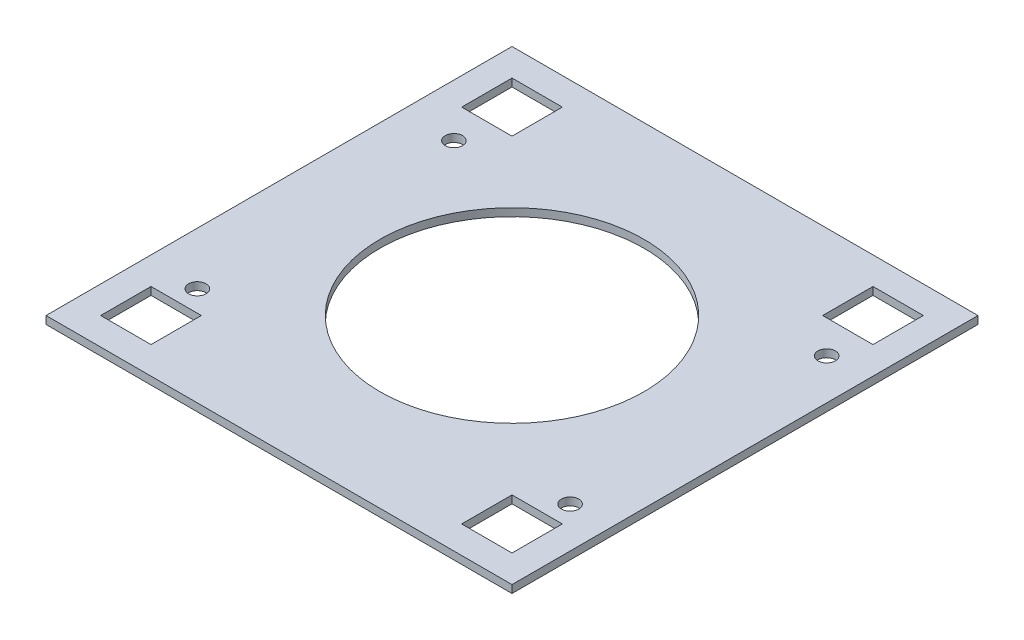
SolidWorks part; units mm, degrees
ref_plane "Front Plane" through (0, 0, 0) normal (0, 0, 1) x (1, 0, 0)
ref_plane "Top Plane" through (0, 0, 0) normal (0, 1, 0) x (1, 0, 0)
ref_plane "Right Plane" through (0, 0, 0) normal (1, 0, 0) x (0, 0, -1)
sketch "Sketch1" plane through (0, 0, 0) normal (0, 1, 0) x (1, 0, 0)
  line L1 (-190.5, 190.5) -> (190.5, 190.5)
  line L2 (-190.5, 190.5) -> (-190.5, -190.5)
  line L3 (-190.5, -190.5) -> (190.5, -190.5)
  line L4 (190.5, 190.5) -> (190.5, -190.5)
  line L5 (-190.5, 190.5) -> (190.5, -190.5) construction
  line L6 (-190.5, -190.5) -> (190.5, 190.5) construction
  point P0 (0, 0)
  dimension "D1" = 381
extrude "Boss-Extrude1" add sketch "Sketch1" along normal blind 6.35
sketch "Sketch2" plane through (0, 6.35, 0) normal (0, 1, 0) x (1, 0, 0)
  circle A0 centre (0, 0) radius 107.95
  dimension "D1" = 215.9
extrude "Cut-Extrude1" cut sketch "Sketch2" against normal blind 6.35
sketch "Sketch3" plane through (0, 6.35, 0) normal (0, 1, 0) x (1, 0, 0)
  line L0 (-190.5, 190.5) -> (190.5, -190.5) construction
  line L1 (127, 127) -> (168.148, 127)
  line L2 (-127, 127) -> (-168.148, 127)
  line L3 (0, 0) -> (0, 50000) construction
  line L4 (0, 0) -> (50000, 0) construction
  line L5 (-190.5, -190.5) -> (190.5, 190.5) construction
  line L6 (147.574, -147.574) -> (-147.574, -147.574) construction
  line L7 (147.574, -147.574) -> (147.574, 147.574) construction
  line L8 (147.574, 147.574) -> (-147.574, 147.574) construction
  line L9 (-147.574, -147.574) -> (-147.574, 147.574) construction
  line L10 (147.574, -147.574) -> (-147.574, 147.574) construction
  line L11 (147.574, 147.574) -> (-147.574, -147.574) construction
  line L12 (-127, 127) -> (-127, 168.148)
  line L13 (-127, 168.148) -> (-168.148, 168.148)
  line L14 (-168.148, 127) -> (-168.148, 168.148)
  line L15 (-127, 127) -> (-168.148, 168.148) construction
  line L16 (-127, 168.148) -> (-168.148, 127) construction
  line L17 (127, 127) -> (127, 168.148)
  line L18 (127, 168.148) -> (168.148, 168.148)
  line L19 (168.148, 127) -> (168.148, 168.148)
  line L20 (127, -127) -> (127, -168.148)
  line L21 (127, -127) -> (168.148, -127)
  line L22 (168.148, -127) -> (168.148, -168.148)
  line L23 (127, -168.148) -> (168.148, -168.148)
  line L24 (-127, -127) -> (-168.148, -127)
  line L25 (-127, -127) -> (-127, -168.148)
  line L26 (-127, -168.148) -> (-168.148, -168.148)
  line L27 (-168.148, -127) -> (-168.148, -168.148)
  line L28 (-147.574, 100.076) -> (157.226, 100.076) construction
  line L29 (-147.574, 100.076) -> (-147.574, -109.728) construction
  circle A4 centre (-147.574, 100.076) radius 7.112
  circle A5 centre (157.226, 100.076) radius 7.112
  circle A6 centre (157.226, -109.728) radius 7.112
  circle A7 centre (-147.574, -109.728) radius 7.112
  point P0 (0, 0)
  point P10 (0, 0)
  point P34 (0, 0)
  dimension "D2" = 41.148
  dimension "D5" = 14.224
  dimension "D1" = 295.148
  dimension "D3" = 41.148
  dimension "D6" = 26.924
  dimension "D9" = 304.8
  dimension "D10" = 209.804
  dimension "D7" = 2
  dimension "D8" = 2
  dimension "D4" = 4
extrude "Cut-Extrude2" cut sketch "Sketch3" against normal blind 6.35 contours L14 L2 L12 L13 | L1 L19 L18 L17 | L20 L23 L22 L21 | L24 L27 L26 L25 region at (147.574, 6.35, -147.574) region at (-147.574, 6.35, -147.574) region at (147.574, 6.35, 147.574) region at (-147.574, 6.35, 147.574)
extrude "Cut-Extrude3" cut sketch "Sketch3<4>" against normal through all contours A5 | A7 | A4 | A6 region at (157.226, 6.35, -100.076) region at (-147.574, 6.35, 109.728)
sketch "Sketch3<4>" plane through (0, 6.35, 0) normal (0, 1, 0) x (1, 0, 0) same geometry as "Sketch3"
